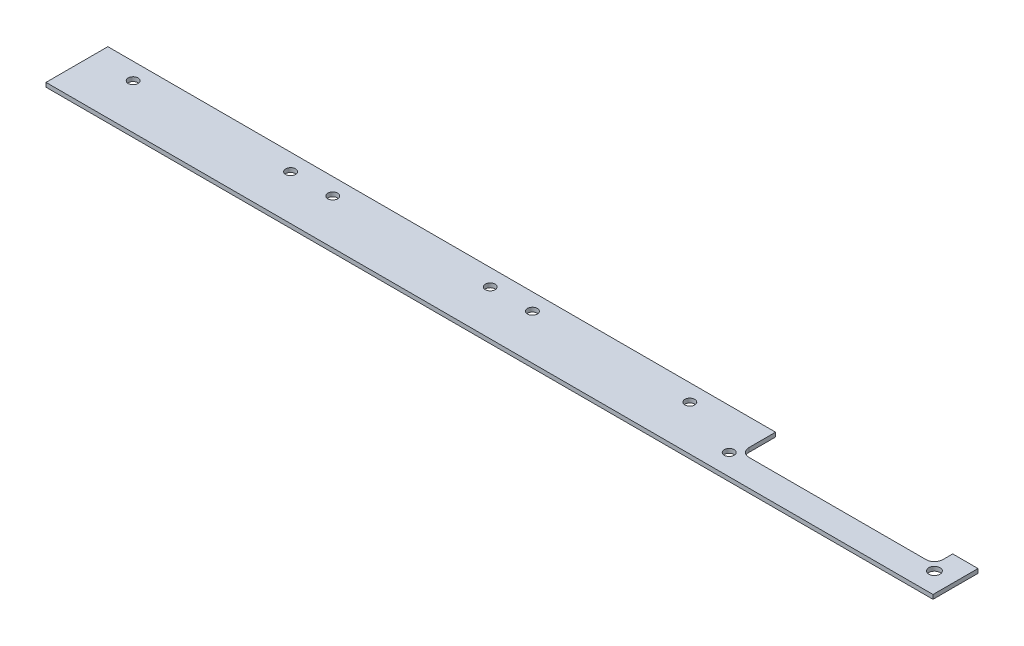
SolidWorks part; units mm, degrees
material "Простая углеродистая сталь"
ref_plane "Спереди" through (0, 0, 0) normal (0, 0, 1) x (1, 0, 0)
ref_plane "Сверху" through (0, 0, 0) normal (0, 1, 0) x (1, 0, 0)
ref_plane "Справа" through (0, 0, 0) normal (1, 0, 0) x (0, 0, -1)
sketch "Эскиз1" plane through (0, 0, 0) normal (0, 1, 0) x (1, 0, 0)
  line L0 (237.5, 22) -> (237.5, 12.5)
  line L1 (0, 0) -> (315.5, 0)
  line L2 (0, 0) -> (0, 22)
  line L3 (0, 22) -> (237.5, 22)
  line L5 (240.5, 9.5) -> (303.5, 9.5)
  line L7 (306.5, 12.5) -> (306.5, 16)
  line L8 (306.5, 16) -> (315.5, 16)
  line L9 (315.5, 16) -> (315.5, 0)
  circle A1 centre (235.5, 7.5) radius 1.75
  circle A2 centre (71, 16) radius 1.75
  circle A3 centre (15, 16) radius 1.75
  circle A4 centre (86, 16) radius 1.75
  circle A5 centre (142, 16) radius 1.75
  circle A8 centre (308.5, 7.5) radius 2
  arc A9 (237.5, 12.5) -> (240.5, 9.5) centre (240.5, 12.5) ccw
  arc A10 (303.5, 9.5) -> (306.5, 12.5) centre (303.5, 12.5) ccw
  circle A11 centre (157, 16) radius 1.75
  circle A12 centre (213, 16) radius 1.75
  dimension "D2" = 3
  dimension "D3" = 3
  dimension "D1" = 3
extrude "Бобышка-Вытянуть1" add sketch "Эскиз1" along normal blind 1.5
